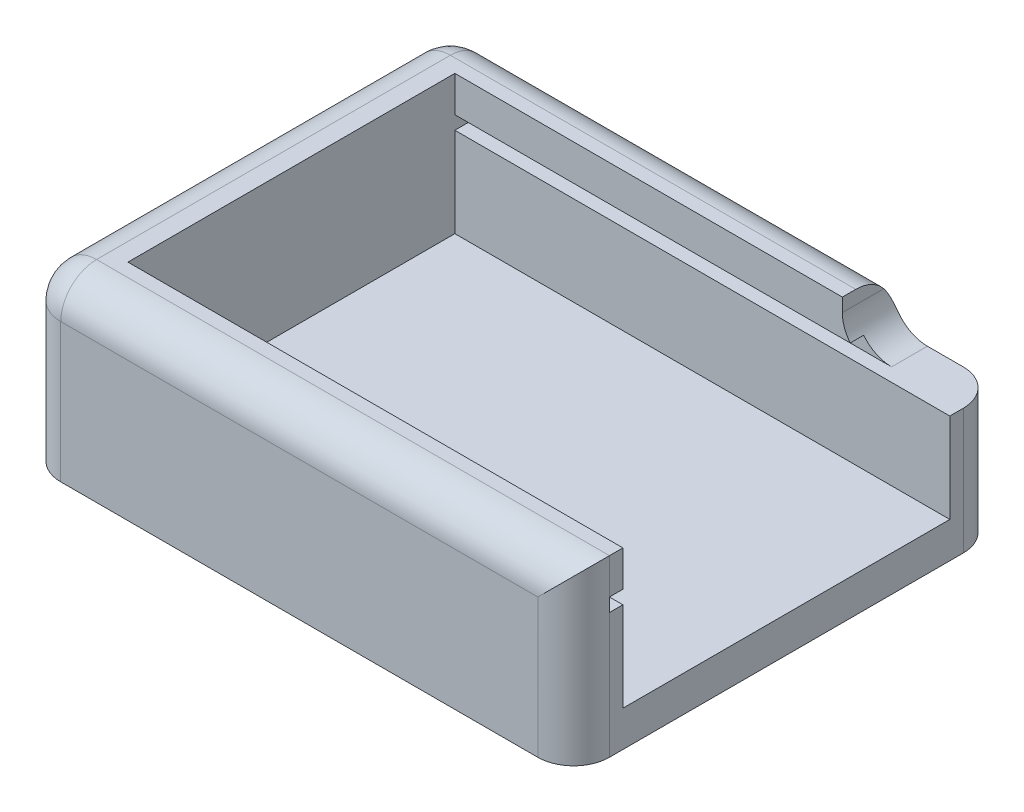
SolidWorks part; units mm, degrees
material "Melamine resin"
ref_plane "Front Plane" through (0, 0, 0) normal (0, 0, 1) x (1, 0, 0)
ref_plane "Top Plane" through (0, 0, 0) normal (0, 1, 0) x (1, 0, 0)
ref_plane "Right Plane" through (0, 0, 0) normal (1, 0, 0) x (0, 0, -1)
sketch "Sketch2" plane through (0, 0, 0) normal (0, 1, 0) x (1, 0, 0)
  line L1 (0, 0) -> (88.9, 0)
  line L2 (0, 0) -> (0, 152.4)
  line L3 (0, 152.4) -> (88.9, 152.4)
  line L10 (88.9, 152.4) -> (88.9, 0)
  dimension "D1" = 152.4
  dimension "D2" = 88.9
extrude "Boss-Extrude1" add sketch "Sketch2" along normal blind 5.9944 contours L3 L10 L1 L2
sketch "Sketch4" plane through (0, 5.9944, 0) normal (0, 1, 0) x (1, 0, 0)
  line L0 (0, 0) -> (0, 152.4) construction
  line L1 (0, 0) -> (88.9, 0) construction
  circle A0 centre (45.72, 109.8713) radius 2.7305
  circle A1 centre (45.72, 33.6713) radius 2.7305
  dimension "D3" = 5.461
  dimension "D4" = 5.461
  dimension "D1" = 76.2
  dimension "D2" = 45.72
  dimension "D5" = 33.6713
extrude "Cut-Extrude2" cut sketch "Sketch4" against normal through all both
ref_plane "Plane1" through (44.45, 0, 0) normal (-1, 0, 0) x (0, 0, 1)
sketch "Sketch6" plane through (44.45, 0, 0) normal (-1, 0, 0) x (0, 0, 1)
  line L0 (0, 5.9944) -> (-152.4, 5.9944) construction
  line L1 (0, 5.9944) -> (-152.4, 5.9944)
  line L3 (-149.86, 5.9944) -> (-89.535, 5.9944)
  line L4 (-149.86, 5.9944) -> (-149.86, 30.7594)
  line L5 (-149.86, 30.7594) -> (-89.535, 30.7594)
  line L6 (-89.535, 5.9944) -> (-89.535, 30.7594)
  line L7 (-142.875, 30.7594) -> (-96.52, 30.7594)
  line L8 (-142.875, 30.7594) -> (-142.875, 11.0744)
  line L9 (-142.875, 11.0744) -> (-96.52, 11.0744)
  line L10 (-96.52, 30.7594) -> (-96.52, 11.0744)
  line L11 (-144.78, 25.6794) -> (-94.615, 25.6794)
  line L12 (-144.78, 25.6794) -> (-144.78, 23.7744)
  line L13 (-144.78, 23.7744) -> (-94.615, 23.7744)
  line L14 (-94.615, 25.6794) -> (-94.615, 23.7744)
  line L15 (-152.4, 5.9944) -> (-152.4, 0) construction
  dimension "D1" = 50.165
  dimension "D2" = 1.905
  dimension "D3" = 1.905
  dimension "D4" = 1.905
  dimension "D5" = 5.08
  dimension "D6" = 12.7
  dimension "D7" = 5.08
  dimension "D8" = 5.08
  dimension "D9" = 5.08
  dimension "D10" = 2.54
extrude "Boss-Extrude3" add sketch "Sketch6" along normal mid plane 70.1802 contours L11 L14 L13 L10 L9 L8 L12 L5 L4 L1 L6 region at (44.45, 6.6465, -119.6975)
sketch "Sketch7" plane through (0, 5.9944, 0) normal (0, 1, 0) x (1, 0, 0)
  line L0 (0, 0) -> (88.9, 0) construction
  line L1 (0, 152.4) -> (2.54, 152.4)
  line L2 (0, 152.4) -> (0, 0)
  line L3 (0, 0) -> (2.54, 0)
  line L4 (2.54, 152.4) -> (2.54, 0)
  dimension "D1" = 2.54
extrude "Cut-Extrude3" cut sketch "Sketch7" against normal through all both
sketch "Sketch8" plane through (0, 0, 0) normal (0, -1, 0) x (1, 0, 0)
  line L4 (2.54, 0) -> (2.54, -152.4)
  line L5 (2.54, -152.4) -> (88.9, -152.4)
  line L6 (88.9, -152.4) -> (88.9, 0)
  line L7 (88.9, 0) -> (2.54, 0)
  line L8 (2.54, 0) -> (2.54, -152.4)
  line L9 (2.54, -152.4) -> (88.9, -152.4)
  line L10 (88.9, -152.4) -> (88.9, 0)
  line L11 (88.9, 0) -> (2.54, 0)
  circle A0 centre (45.72, -33.6713) radius 2.7305 construction
  circle A1 centre (45.72, -33.6713) radius 2.7305
  circle A2 centre (45.72, -109.8713) radius 2.7305 construction
  circle A3 centre (45.72, -109.8713) radius 2.7305
  dimension "D1" = 0
extrude "Cut-Extrude5" cut sketch "Sketch8" against normal up to surface (5.9944 mm away) up to face at (45.72, 5.9944, -76.2)
sketch "Sketch9" plane through (0, 5.9944, 0) normal (0, -1, 0) x (1, 0, 0)
  line L0 (44.45, 10.9153) -> (44.45, -10.9153) construction
  line L1 (44.45, -94.2975) -> (44.45, -145.0975) construction
  line L2 (79.5401, -89.535) -> (79.5401, -149.86) construction
  circle A0 centre (44.45, -94.2975) radius 2.7305
  circle A1 centre (44.45, -145.0975) radius 2.7305
  point P8 (79.5401, -119.6975)
  point P9 (44.45, -119.6975)
  dimension "D1" = 5.461
  dimension "D2" = 5.461
  dimension "D3" = 50.8
extrude "Cut-Extrude6" cut sketch "Sketch9" against normal blind 4.064
sketch "Sketch11" plane through (9.3599, 0, 0) normal (-1, 0, 0) x (0, 0, 1)
  line L0 (-89.535, 5.9944) -> (-89.535, 30.7594) construction
  line L5 (-149.86, 5.9944) -> (-89.535, 5.9944)
  line L6 (-149.86, 5.9944) -> (-149.86, 30.7594)
  line L7 (-149.86, 30.7594) -> (-89.535, 30.7594)
  line L8 (-89.535, 5.9944) -> (-89.535, 30.7594)
  line L10 (-149.86, 30.7594) -> (-142.875, 30.7594) construction
extrude "Boss-Extrude4" add sketch "Sketch11" along normal blind 7.62
fillet "Fillet1" radius 5.08 7 edges at (79.5401, 18.3769, -149.86) (79.5401, 18.3769, -89.535) (1.7399, 18.3769, -149.86) (1.7399, 18.3769, -89.535) (40.64, 30.7594, -89.535) (1.7399, 30.7594, -119.6975) (40.64, 30.7594, -149.86)
sketch "Sketch13" plane through (0, 0, -142.875) normal (0, 0, 1) x (1, 0, 0)
  line L1 (79.5401, 30.7594) -> (64.3001, 30.7594)
  line L2 (79.5401, 30.7594) -> (79.5401, 23.7744)
  line L3 (79.5401, 23.7744) -> (64.3001, 23.7744)
  line L4 (64.3001, 30.7594) -> (64.3001, 23.7744)
  line L5 (9.3599, 23.7744) -> (79.5401, 23.7744) construction
  point P7 (0, 0)
  dimension "D1" = 15.24
extrude "Cut-Extrude8" cut sketch "Sketch13" against normal through all
fillet "Fillet2" radius 5.08 1 edges at (64.3001, 23.7744, -147.32)
equation "\"threaded_insert_hole\"=0.1472"
equation "\"th\"=1.25249"
